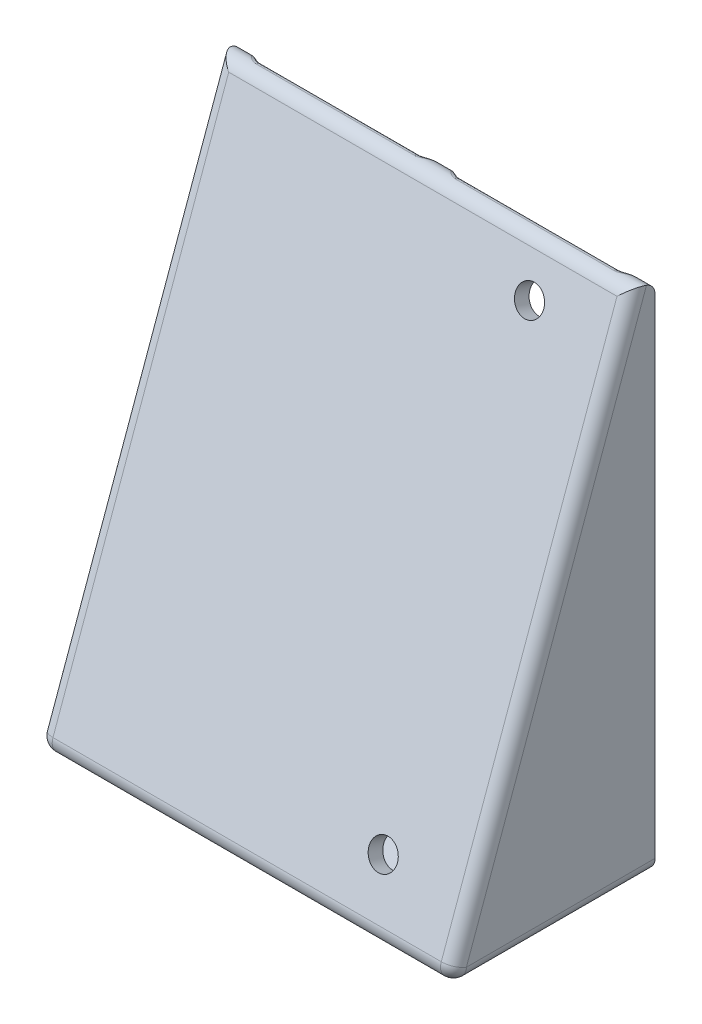
SolidWorks part; units mm, degrees
material "ABS"
ref_plane "X-Y Datum" through (0, 0, 0) normal (0, 0, 1) x (1, 0, 0)
ref_plane "X-Z Datum" through (0, 0, 0) normal (0, 1, 0) x (1, 0, 0)
ref_plane "Y-Z Datum" through (0, 0, 0) normal (1, 0, 0) x (0, 0, -1)
sketch "Sketch1" plane through (0, 0, 0) normal (1, 0, 0) x (0, 0, -1)
  line L0 (0, 0) -> (-50.8, 0)
  line L1 (-50.8, 0) -> (0, 141.1797)
  line L2 (0, 141.1797) -> (0, 0)
  dimension "D1" = 50.8
  dimension "D2" = 70.21
extrude "Boss-Extrude1" add sketch "Sketch1" along normal blind 101.6
fillet "Fillet1" [suppressed] radius 15.24
ref_plane "Plane2" through (50.8, 0, 0) normal (1, 0, 0) x (0, 0, -1)
sketch "Sketch3" plane through (50.8, 0, 0) normal (1, 0, 0) x (0, 0, -1)
  line L0 (-45.3799, 3.81) -> (0, 129.9266)
  line L2 (0, 129.9266) -> (0, 3.81)
  line L3 (0, 0) -> (0, 141.1797) construction
  line L4 (0, 3.81) -> (-45.3799, 3.81)
  line L5 (0, 141.1797) -> (-50.8, 0) construction
  line L6 (-45.3799, 3.81) -> (-45.3799, 0) construction
  line L7 (-50.8, 0) -> (0, 0) construction
  line L8 (-45.3799, 3.81) -> (-48.9649, 5.1) construction
  point P8 (9.4574, 156.21)
  point P13 (0, 0)
  point P14 (0, 0)
  dimension "D1" = 3.81
extrude "Cut-Extrude1" cut sketch "Sketch3" against normal offset from surface (45.085 mm away) 3.81 from offset 1.905 up to face at (0, 47.0599, 16.9333) offset against normal yes
extrude "Cut-Extrude2" cut sketch "Sketch3<3>" along normal offset from surface (45.085 mm away) 3.81 from offset 1.905 up to face at (101.6, 47.0599, 16.9333)
sketch "Sketch3<3>" plane through (50.8, 0, 0) normal (1, 0, 0) x (0, 0, -1) same geometry as "Sketch3"
fillet "Fillet5" radius 3.175 15 edges at (52.705, 3.81, 22.69) (3.81, 3.81, 22.69) (48.895, 3.81, 22.69) (97.79, 3.81, 22.69) (97.79, 66.8683, 22.69) (48.895, 66.8683, 22.69) (52.705, 66.8683, 22.69) (3.81, 66.8683, 22.69) (75.2475, 3.81, 45.3799) (26.3525, 3.81, 45.3799) (101.6, 70.5899, 25.4) (0, 70.5899, 25.4) (0, 0, 25.4) (50.8, 0, 50.8) (101.6, 0, 25.4)
sketch "Sketch5" plane through (0, 16.1837, 44.9767) normal (0, 0.3386, 0.9409) x (1, 0, 0)
  line L0 (80.0355, 105.5653) -> (80.0362, -0.4337) construction
  line L1 (3.175, -12.6828) -> (98.425, -12.6828) construction
  circle A1 centre (80.0355, 105.5653) radius 3.5
  circle A2 centre (80.0362, -0.4337) radius 3.5
  point P4 (0, 0)
  dimension "D3" = 7
  dimension "D6" = 7
  dimension "D1" = 80.0362
  dimension "D2" = 0.4337
  dimension "D4" = 105.999
  dimension "D5" = 90
extrude "Cut-Extrude4" cut sketch "Sketch5" against normal up to next
sketch "Sketch6" plane through (0, 3.81, 0) normal (0, 1, 0) x (1, 0, 0)
  line L0 (94.615, 0) -> (55.88, 0) construction
  line L1 (66.675, -12.7) -> (34.925, -12.7) construction
  line L2 (50.8, -25.4558) -> (50.8, 25.4558) construction
  line L3 (85.725, -31.75) -> (15.875, -31.75) construction
  circle A0 centre (66.675, -12.7) radius 1.5875
  circle A1 centre (34.925, -12.7) radius 1.5875
  circle A2 centre (85.725, -31.75) radius 1.5875
  circle A3 centre (15.875, -31.75) radius 1.5875
  point P6 (50.8, -12.7)
  point P13 (50.8, -31.75)
  dimension "D3" = 3.175
  dimension "D1" = 12.7
  dimension "D2" = 31.75
  dimension "D4" = 69.85
  dimension "D5" = 19.05
extrude "Cut-Extrude5" cut sketch "Sketch6" against normal up to next
fillet "Fillet6" radius 3.175 1 edges at (50.8, 141.1797, 0) tangent propagation no
fillet "Fillet7" radius 1.27 20 edges at (4.9282, 125.1927, 0.8996) (3.8372, 121.7743, 0) (3.81, 63.767, 0) (4.7399, 4.7399, 0) (26.3525, 3.81, 0) (47.9651, 4.7399, 0) (48.895, 63.767, 0) (48.8678, 121.7743, 0) (48.2512, 124.7356, 0.5306) (53.8232, 125.1927, 0.8996) (52.7322, 121.7743, 0) (52.705, 63.767, 0) (53.6349, 4.7399, 0) (75.2475, 3.81, 0) (96.8601, 4.7399, 0) (97.79, 63.767, 0) (97.7628, 121.7743, 0) (97.1462, 124.7356, 0.5306) (26.3525, 125.6906, 1.5243) (75.2475, 125.6906, 1.5243)
